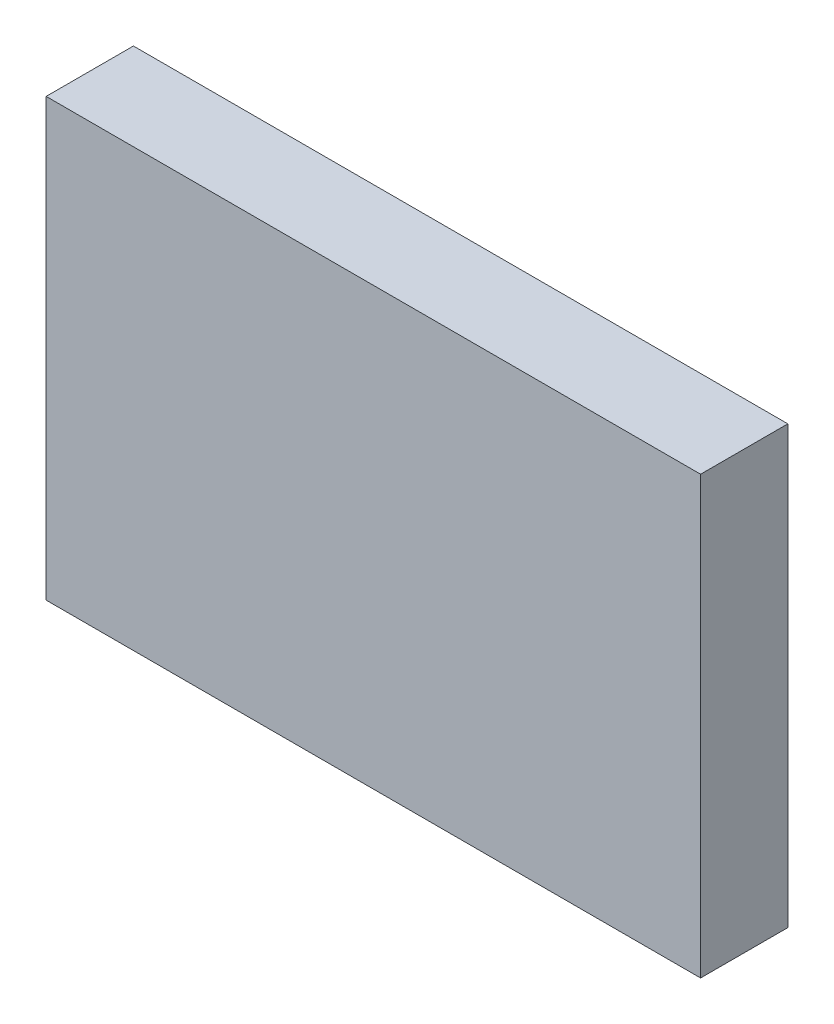
SolidWorks part; units mm, degrees
material "Лист 4,0 ГОСТ 19903-2015 / Ст3сп ГОСТ 14637-89"
ref_plane "Спереди" through (0, 0, 0) normal (0, 0, 1) x (1, 0, 0)
ref_plane "Сверху" through (0, 0, 0) normal (0, 1, 0) x (1, 0, 0)
ref_plane "Справа" through (0, 0, 0) normal (1, 0, 0) x (0, 0, -1)
sketch "Эскиз1" plane through (0, 0, 0) normal (0, 0, 1) x (1, 0, 0)
  line L1 (-15, -10) -> (15, -10)
  line L2 (-15, -10) -> (-15, 10)
  line L3 (-15, 10) -> (15, 10)
  line L4 (15, -10) -> (15, 10)
extrude "Бобышка-Вытянуть1" add sketch "Эскиз1" along normal blind 4
